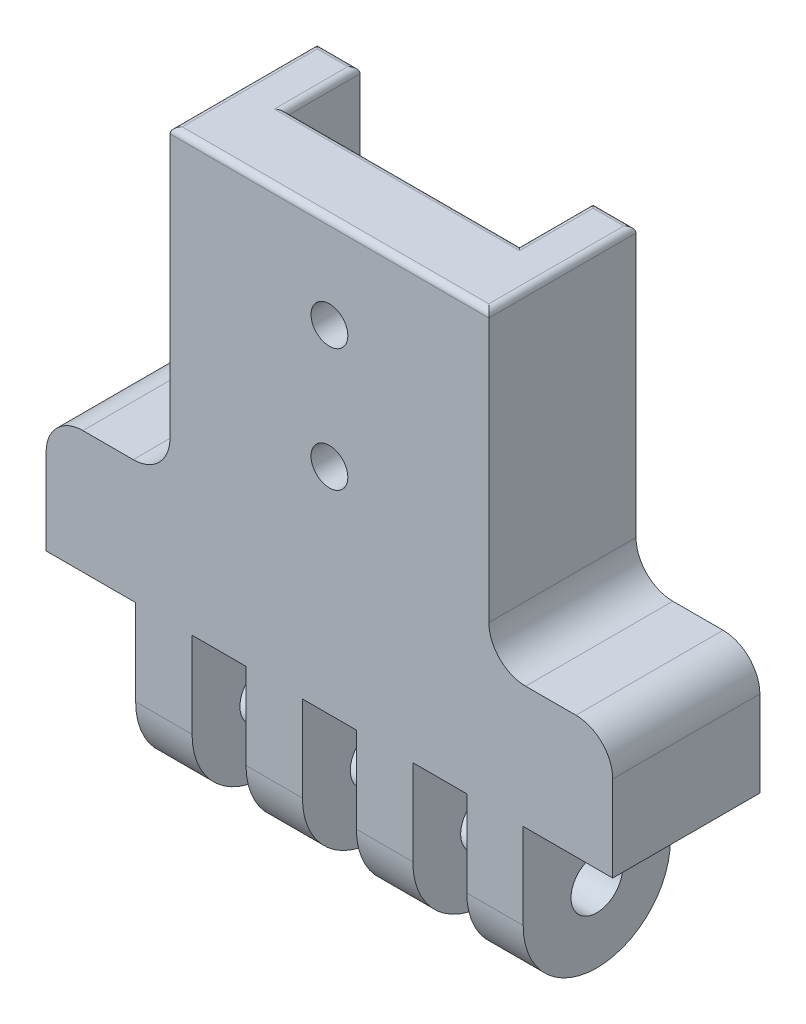
SolidWorks part; units mm, degrees
other "Markup1"
sketch "Sketch9" plane through (-23.1, -13, 8) normal (-0.4776, -0.6311, 0.6112) x (-0.7397, -0.0865, -0.6673)
ref_plane "Front Plane" through (0, 0, 0) normal (0, 0, 1) x (1, 0, 0)
ref_plane "Top Plane" through (0, 0, 0) normal (0, 1, 0) x (1, 0, 0)
ref_plane "Right Plane" through (0, 0, 0) normal (1, 0, 0) x (0, 0, -1)
sketch "Sketch1" plane through (0, 0, 0) normal (0, 1, 0) x (1, 0, 0)
  line L1 (23.1, 6) -> (-23.1, 6)
  line L2 (23.1, 6) -> (23.1, -6)
  line L3 (23.1, -6) -> (-23.1, -6)
  line L4 (-23.1, 6) -> (-23.1, -6)
  line L5 (23.1, 6) -> (-23.1, -6) construction
  line L6 (23.1, -6) -> (-23.1, 6) construction
  point P0 (0, 0)
  dimension "D1" = 12
  dimension "D2" = 46.2
extrude "Boss-Extrude1" add sketch "Sketch1" along normal blind 10
sketch "Sketch2" plane through (0, 0, 0) normal (0, -1, 0) x (1, 0, 0)
  line L0 (23.1, -6) -> (-23.1, -6) construction
  line L1 (15.8, -6) -> (11.2, -6)
  line L2 (15.8, -6) -> (15.8, 6)
  line L3 (15.8, 6) -> (11.2, 6)
  line L4 (11.2, -6) -> (11.2, 6)
  line L5 (13.5, 8) -> (13.5, -6) construction
  line L6 (15.8, 0) -> (11.2, 0) construction
  point P272 (13.5, 0)
  dimension "D1" = 12
  dimension "D2" = 4.6
extrude "Boss-Extrude2" add sketch "Sketch2" along normal blind 7
sketch "Sketch8" plane through (15.8, 0, 0) normal (1, 0, 0) x (0, 0, -1)
  line L0 (6, -7) -> (-6, -7) construction
  line L1 (6, -7) -> (6, 0) construction
  circle A0 centre (0, -7) radius 6
  dimension "D1" = 12
extrude "Boss-Extrude3" add sketch "Sketch8" against normal up to surface (4.6 mm away) up to face at (11.2, -3.5, 0)
pattern_linear "LPattern1" count 4 spacing 9 along (-1, 0, 0) of "Boss-Extrude2", "Boss-Extrude3"
sketch "Sketch4" plane through (15.8, 0, 0) normal (1, 0, 0) x (0, 0, -1)
  circle A0 centre (0, -7) radius 2.1
  arc A2 (-6, -7) -> (6, -7) centre (0, -7) ccw construction
  dimension "D1" = 4.2
  dimension "D2" = 0
extrude "Cut-Extrude1" cut sketch "Sketch4" against normal through all
ref_plane "Plane1" through (0, 10, 0) normal (0, 1, 0) x (1, 0, 0)
sketch "Sketch10" plane through (0, 10, 0) normal (0, 1, 0) x (1, 0, 0)
  line L0 (23.1, 6) -> (-23.1, 6) construction
  line L1 (13, -6) -> (-13, -6)
  line L2 (13, -6) -> (13, 6)
  line L3 (13, 6) -> (-13, 6)
  line L4 (-13, -6) -> (-13, 6)
  line L5 (13, -6) -> (-13, 6) construction
  line L6 (13, 6) -> (-13, -6) construction
  point P0 (0, 0)
  dimension "D1" = 26
extrude "Boss-Extrude4" add sketch "Sketch10" along normal blind 25
ref_plane "Plane2" through (0, 35, 0) normal (0, 1, 0) x (1, 0, 0)
sketch "Sketch11" plane through (0, 35, 0) normal (0, 1, 0) x (1, 0, 0)
  line L0 (13, 6) -> (-13, 6) construction
  line L1 (9.5, 0) -> (-9.5, 0)
  line L2 (9.5, 0) -> (9.5, 6)
  line L3 (9.5, 6) -> (-9.5, 6)
  line L4 (-9.5, 0) -> (-9.5, 6)
  line L5 (9.5, 0) -> (-9.5, 6) construction
  line L6 (9.5, 6) -> (-9.5, 0) construction
  line L7 (-13, 6) -> (-13, -6) construction
  point P0 (0, 3)
  point P7 (-9.5, 3)
  dimension "D1" = 19
  dimension "D2" = 6
  dimension "D3" = 13
extrude "Cut-Extrude2" cut sketch "Sketch11" against normal blind 25
fillet "Fillet1" radius 3 4 edges at (-13, 10, 0) (13, 10, 0) (23.1, 10, 0) (-23.1, 10, 0)
fillet "Fillet2" radius 0.5 8 edges at (-13, 35, 0) (-11.25, 35, -6) (-9.5, 35, -3) (0, 35, 0) (9.5, 35, -3) (11.25, 35, -6) (13, 35, 0) (0, 35, 6)
sketch "Sketch12" plane through (0, 0, 0) normal (0, 0, 1) x (1, 0, 0)
  line L0 (-18.4905, 22.5) -> (19.9775, 22.5) construction
  line L1 (-20.1, 10) -> (-16, 10) construction
  line L2 (13, 34.5) -> (13, 13) construction
  circle A0 centre (0, 17.5) radius 1.5
  circle A1 centre (0, 27.5) radius 1.5
  dimension "D1" = 3
  dimension "D2" = 10
  dimension "D3" = 5
  dimension "D4" = 12.5
  dimension "D5" = 13
extrude "Cut-Extrude3" cut sketch "Sketch12" against normal mid plane 20
